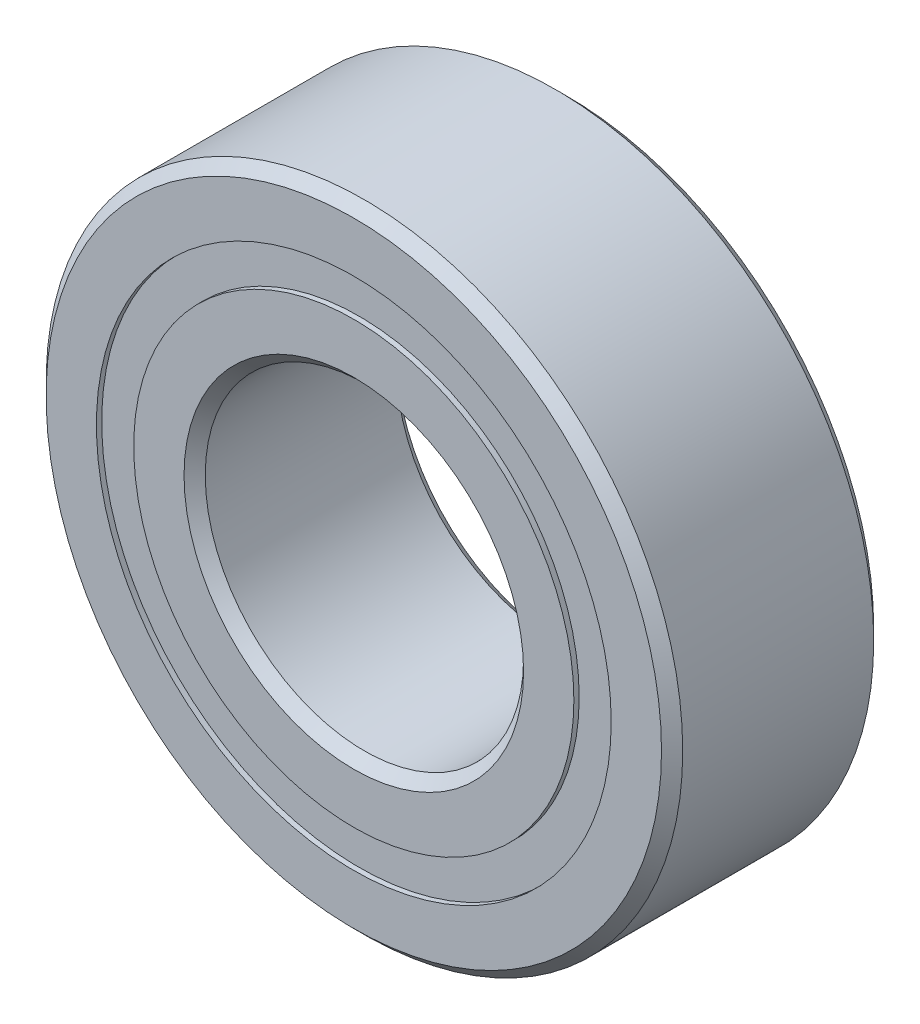
SolidWorks part; units mm, degrees
note: '?' marks a value the reader was unsure of.
ref_plane "Front Plane" through (0, 0, 0) normal (0, 0, 1) x (1, 0, 0)
ref_plane "Top Plane" through (0, 0, 0) normal (0, 1, 0) x (1, 0, 0)
ref_plane "Right Plane" through (0, 0, 0) normal (1, 0, 0) x (0, 0, -1)
sketch "Sketch1" plane through (0, 0, 0) normal (1, 0, 0) x (0, 0, -1)
  line L0 (-2, 0) -> (2, 0) construction
  line L1 (0, 6) -> (0, -6) construction
  line L2 (1.8, 6) -> (-1.8, 6)
  line L3 (-1.8, 6) -> (-2, 5.8)
  line L4 (-2, 5.8) -> (-2, 4.8516)
  line L5 (-2, 4.8516) -> (-0.8889, 4.8516)
  line L6 (2, 4.8516) -> (0.8889, 4.8516)
  line L7 (2, 5.8) -> (2, 4.8516)
  line L8 (1.8, 6) -> (2, 5.8)
  line L9 (0, 6) -> (0, 4.5) construction
  line L10 (0, 4.5) -> (0, 3) construction
  arc A0 (-0.8889, 4.8516) -> (0.8889, 4.8516) centre (0, 4.5) cw
  point P14 (0, 3)
  dimension "Width" = 4
  dimension "OD" = 12
  dimension "D1" = 45
  dimension "D2" = 0.2
  dimension "Shaft Dia" = 6
  dimension "D3" = 1.7778
  dimension "D4" = 0.3516
revolve "Revolve1" add sketch "Sketch1" angle 360 about L0
sketch "Sketch3" plane through (0, 0, 0) normal (1, 0, 0) x (0, 0, -1)
  line L0 (-2, 4.1484) -> (-0.8889, 4.1484)
  line L1 (0, 6) -> (0, -6) construction
  line L2 (-2, 5.8) -> (-2, 4.8516) construction
  line L3 (-2, 4.1484) -> (-2, 3.2)
  line L4 (-1.8, 6) -> (-2, 5.8) construction
  line L5 (-2, 3.2) -> (-1.8, 3)
  line L6 (-1.8, 3) -> (1.8, 3)
  line L7 (1.8, 6) -> (1.8, -6) construction
  line L8 (1.8, 3) -> (2, 3.2)
  line L9 (2, -5.8) -> (2, 5.8) construction
  line L10 (2, 3.2) -> (2, 4.1484)
  line L11 (2, 4.1484) -> (0.8889, 4.1484)
  line L13 (1.8, 6) -> (2, 5.8) construction
  arc A0 (0.8889, 4.8516) -> (-0.8889, 4.8516) centre (0, 4.5) ccw construction
  arc A1 (0.8889, 4.1484) -> (-0.8889, 4.1484) centre (0, 4.5) cw
revolve "Revolve3" add sketch "Sketch3" angle 360 about L0
sketch "Sketch4" plane through (0, 0, 0) normal (1, 0, 0) x (0, 0, -1)
  line L0 (-0.9559, 4.5) -> (0.9559, 4.5)
  arc A2 (-0.9559, 4.5) -> (0.9559, 4.5) centre (0, 4.5) cw
  arc A3 (0.8889, 4.8516) -> (-0.8889, 4.8516) centre (0, 4.5) ccw construction
revolve "Revolve4" add sketch "Sketch4" angle 360 about L0
ref_axis "Axis1" through (0, 0, -2) along (0, 0, 1)?
pattern_circular "CirPattern1" count 12 every 30 about axis through (0, 0, 0) along (0, 0, 1) of bodies 104
sketch "Sketch5" plane through (0, 0, 0) normal (1, 0, 0) x (0, 0, -1)
  line L0 (-2, 4.8516) -> (-0.8889, 4.8516) construction
  line L1 (-1.9, 4.8516) -> (-0.9559, 4.8516)
  line L2 (-1.9, 4.8516) -> (-1.9, 4.1484)
  line L3 (-1.9, 4.1484) -> (-0.9559, 4.1484)
  line L4 (-0.9559, 4.8516) -> (-0.9559, 4.1484)
  line L5 (-2, 4.1484) -> (-0.8889, 4.1484) construction
  line L6 (2, 4.8516) -> (0.8889, 4.8516) construction
  line L7 (1.9, 4.8516) -> (0.9559, 4.8516)
  line L8 (1.9, 4.8516) -> (1.9, 4.1484)
  line L9 (1.9, 4.1484) -> (0.9559, 4.1484)
  line L10 (0.9559, 4.8516) -> (0.9559, 4.1484)
  line L11 (2, 4.1484) -> (0.8889, 4.1484) construction
  line L12 (-1.8, 6) -> (-2, 5.8) construction
  point P18 (-1.9, 5.9)
revolve "Revolve5" add sketch "Sketch5" angle 360 about L0
sketch "Sketch6" plane through (0, 0, 0) normal (1, 0, 0) x (0, 0, -1)
  line L0 (2, 0) -> (-2, 0) construction
  line L1 (2, 4.8516) -> (0.9, 4.8516)
  line L2 (2, 4.8516) -> (2, 9.5)
  line L3 (2, 9.5) -> (0.9, 9.5)
  line L4 (0.9, 4.8516) -> (0.9, 9.5)
  dimension "Th" = 1.1
  dimension "Flange OD" = 19
revolve "Revolve6" [suppressed] add sketch "Sketch6" angle 360 about L0
equation "\"D2@Sketch1\" = \"Width@Sketch1\"*.05"
equation "\"D3@Sketch1\" = \"Width@Sketch1\"/2.25"
equation "\"D4@Sketch1\" = (((\"OD@Sketch1\"-\"Width@Sketch1\")/2)/3.25)/3.5"
equation "\"D2@CirPattern1\" = 360/\"Balls@CirPattern1\""
